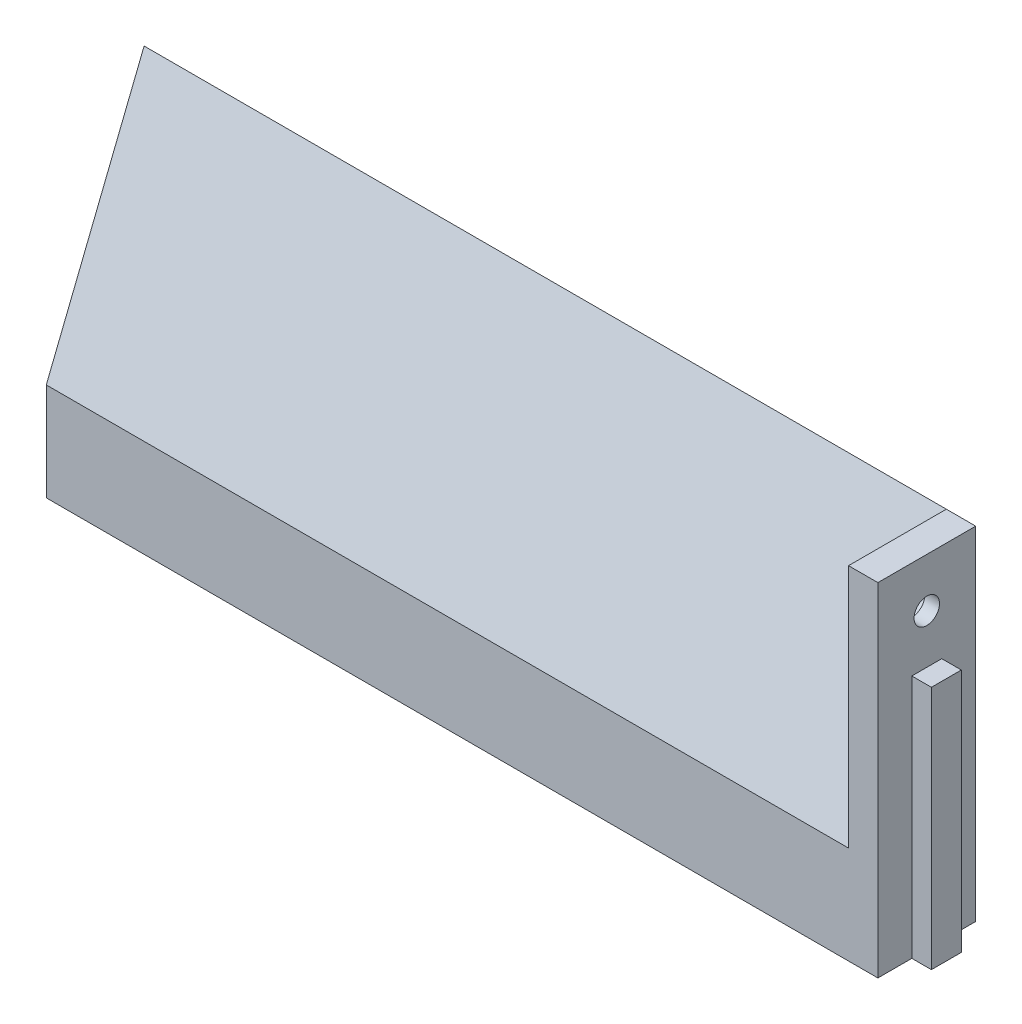
SolidWorks part; units mm, degrees
ref_plane "前视基准面" through (0, 0, 0) normal (0, 0, 1) x (1, 0, 0)
ref_plane "上视基准面" through (0, 0, 0) normal (0, 1, 0) x (1, 0, 0)
ref_plane "右视基准面" through (0, 0, 0) normal (1, 0, 0) x (0, 0, -1)
other "Configuration Table"
sketch "草图1" plane through (0, 0, 0) normal (0, 1, 0) x (1, 0, 0)
  line L1 (0, 0) -> (170, 0)
  line L2 (0, 0) -> (0, 20)
  line L3 (0, 20) -> (170, 20)
  line L4 (170, 0) -> (170, 20)
extrude "凸台-拉伸1" add sketch "草图1" along normal blind 70
sketch "草图2" plane through (170, 0, 0) normal (1, 0, 0) x (0, 0, -1)
  line L0 (20, 70) -> (20, 0) construction
  line L1 (0, 0) -> (20, 0)
  line L2 (0, 0) -> (0, 20)
  line L3 (0, 20) -> (20, 20)
  line L4 (20, 0) -> (20, 20)
  line L5 (0, 20) -> (20, 70)
  line L6 (20, 70) -> (0, 70)
  line L7 (0, 70) -> (0, 20)
  line M7 (20, 70) -> (0, 70)
  line M8 (0, 70) -> (0, 0)
extrude "切除-拉伸1" cut sketch "草图2" against normal blind 164 contours L5 M8 M7 region at (170, 53.3333, -6.6667)
sketch "草图3" plane through (6, 0, 0) normal (1, 0, 0) x (0, 0, -1)
  line L0 (10, 70) -> (10, 60)
  line L1 (20, 70) -> (0, 70) construction
  circle A0 centre (10, 60) radius 5
extrude "切除-拉伸2" cut sketch "草图3" against normal blind 3 contours A0 region at (6, 56.5645, -6.5645)
sketch "草图4" plane through (3, 0, 0) normal (1, 0, 0) x (0, 0, -1)
  circle A0 centre (10, 60) radius 2.6
extrude "切除-拉伸3" cut sketch "草图4" against normal blind 3
sketch "草图5" plane through (0, 0, 0) normal (-1, 0, 0) x (0, 0, 1)
  line L0 (-10, 70) -> (-10, 60)
  line L1 (-20, 70) -> (0, 70) construction
  line L2 (-10, 60) -> (-10, 50)
  line L3 (-10, 50) -> (-6.94, 50)
  line L4 (-10, 50) -> (-10, 0)
  line L5 (-20, 0) -> (0, 0) construction
  line L6 (-10, 0) -> (-13.06, 0)
  line L8 (-6.94, 50) -> (-13.06, 50)
  line L9 (-6.94, 50) -> (-6.94, 0)
  line L10 (-6.94, 0) -> (-13.06, 0)
  line L11 (-13.06, 50) -> (-13.06, 0)
  line M9 (-20, 0) -> (0, 0)
extrude "凸台-拉伸2" add sketch "草图5" along normal blind 4 contours L8 L11 L4 M9 | L9 L3 L4 M9 region at (0, 25, -8.47) region at (0, 25, -11.53)
mirror "镜向1" about plane through (170, 70, 0) normal (-1, 0, 0) of "凸台-拉伸1", "切除-拉伸1", "切除-拉伸2", "切除-拉伸3", "凸台-拉伸2"
sketch "草图6" plane through (0, 0, 0) normal (0, -1, 0) x (1, 0, 0)
  line L0 (340, -20) -> (0, -20) construction
  line L1 (0, 0) -> (170, 0)
  line L2 (0, 0) -> (0, -20)
  line L3 (0, -20) -> (170, -20)
  line L4 (170, 0) -> (170, -20)
  line L6 (0, -6.94) -> (-4, -6.94)
  line L7 (0, -6.94) -> (0, -13.06)
  line L8 (0, -13.06) -> (-4, -13.06)
  line L9 (-4, -6.94) -> (-4, -13.06)
  line M5 (0, -13.06) -> (0, -20)
  line M6 (0, -20) -> (340, -20)
  line M12 (340, 0) -> (0, 0)
  line M13 (0, 0) -> (0, -6.94)
  line M14 (0, -6.94) -> (-4, -6.94)
  line M15 (-4, -6.94) -> (-4, -13.06)
  line M16 (-4, -13.06) -> (0, -13.06)
extrude "切除-拉伸4" cut sketch "草图6" against normal blind 200 contours L4 L2 M12 M13 M5 M6 | L2 M14 M15 M16 region at (85, 0, -10) region at (-2, 0, -10)
